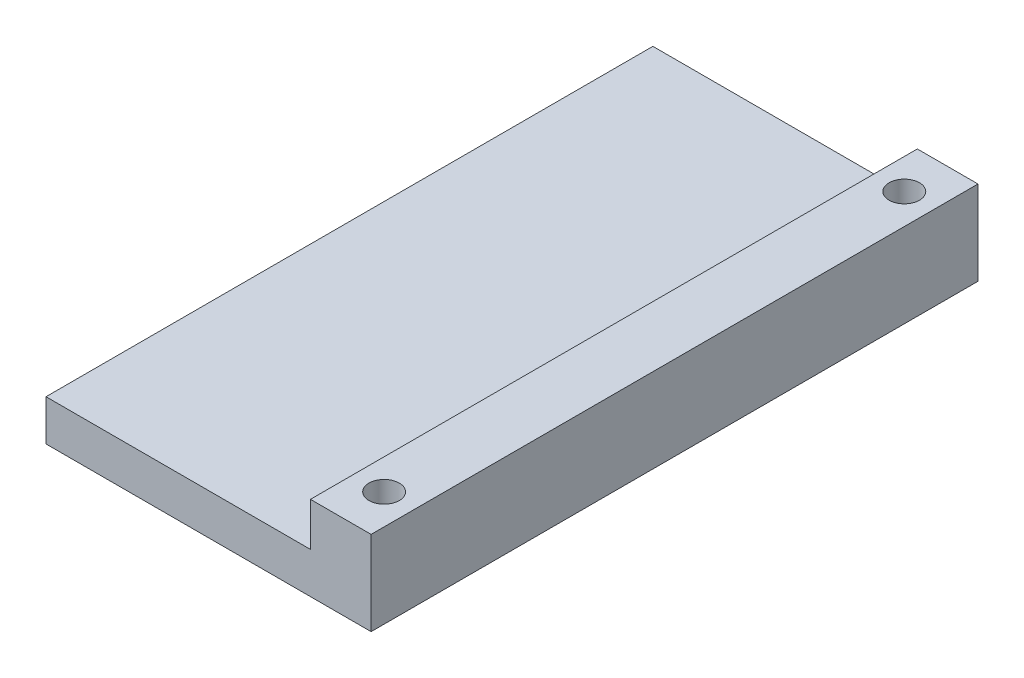
SolidWorks part; units mm, degrees
ref_plane "Front Plane" through (0, 0, 0) normal (0, 0, 1) x (1, 0, 0)
ref_plane "Top Plane" through (0, 0, 0) normal (0, 1, 0) x (1, 0, 0)
ref_plane "Right Plane" through (0, 0, 0) normal (1, 0, 0) x (0, 0, -1)
sketch "Sketch1" plane through (0, 0, 0) normal (0, 1, 0) x (1, 0, 0)
  line L1 (0, 0) -> (41.275, 0)
  line L2 (0, 0) -> (0, 88.9)
  line L3 (0, 88.9) -> (41.275, 88.9)
  line L4 (41.275, 0) -> (41.275, 88.9)
  line L5 (41.275, 88.9) -> (50.165, 88.9)
  line L6 (41.275, 88.9) -> (41.275, 0)
  line L7 (41.275, 0) -> (50.165, 0)
  line L8 (50.165, 88.9) -> (50.165, 0)
  dimension "D1" = 41.275
  dimension "D2" = 88.9
  dimension "D3" = 8.89
extrude "Boss-Extrude1" add sketch "Sketch1" along normal blind 5.9944 contours L1 L4 L3 L2 region at (20.6375, 0, -44.45)
extrude "Boss-Extrude2" add sketch "Sketch1<5>" along normal blind 12.3444 contours L8 L5 L4 L7 region at (45.72, 0, -44.45)
sketch "Sketch1<5>" plane through (0, 0, 0) normal (0, 1, 0) x (1, 0, 0) same geometry as "Sketch1"
sketch "Sketch3" plane through (0, 12.3444, 0) normal (0, 1, 0) x (1, 0, 0)
  line L0 (45.72, 82.55) -> (45.72, 6.35) construction
  line L1 (50.165, 88.9) -> (50.165, 0) construction
  line L2 (41.275, 88.9) -> (50.165, 88.9) construction
  line L3 (0, 0) -> (0, 88.9) construction
  circle A0 centre (45.72, 82.55) radius 2.2225
  circle A1 centre (45.72, 6.35) radius 2.2225
  point P4 (45.72, 44.45)
  point P6 (50.165, 44.45)
  point P7 (45.72, 88.9)
  dimension "D1" = 4.445
  dimension "D2" = 4.445
  dimension "D3" = 76.2
  dimension "D4" = 45.72
extrude "Cut-Extrude1" cut sketch "Sketch3" against normal through all both contours A1 | A0
sketch "Sketch4" plane through (0, 0, 0) normal (0, -1, 0) x (1, 0, 0)
  circle A0 centre (45.72, -6.35) radius 3.683
  circle A1 centre (45.72, -82.55) radius 3.683
  dimension "D1" = 7.366
  dimension "D2" = 7.366
extrude "Cut-Extrude2" cut sketch "Sketch4" against normal blind 4.064
sketch "Sketch5" plane through (0, 5.9944, 0) normal (0, 1, 0) x (1, 0, 0)
  line L0 (0, 0) -> (41.275, 0) construction
  line L1 (0, 88.9) -> (2.54, 88.9)
  line L2 (0, 88.9) -> (0, 0)
  line L3 (0, 0) -> (2.54, 0)
  line L4 (2.54, 88.9) -> (2.54, 0)
  dimension "D1" = 2.54
extrude "Cut-Extrude3" cut sketch "Sketch5" against normal through all both
